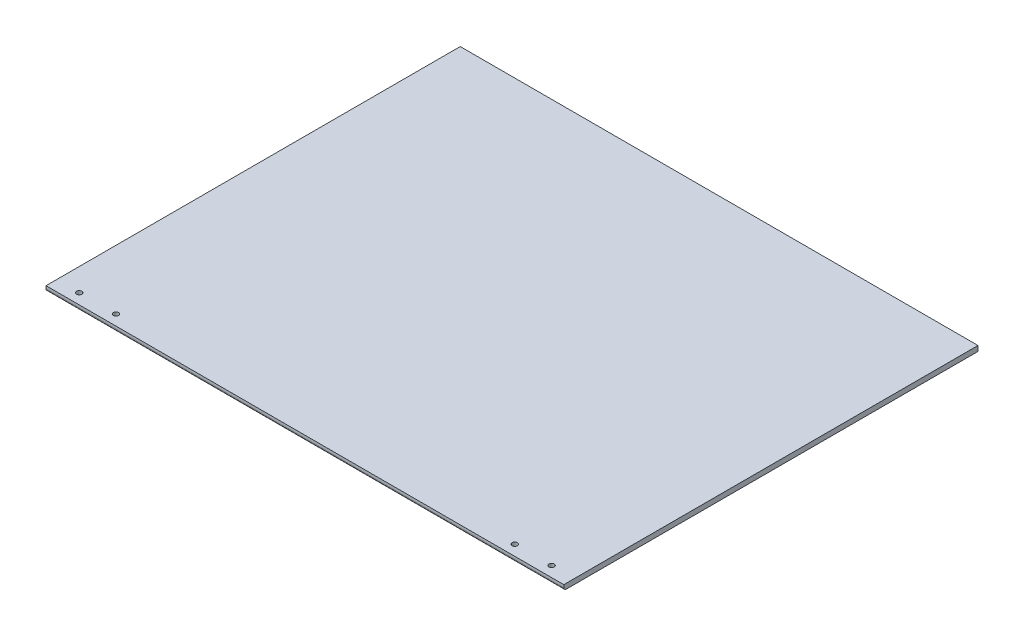
SolidWorks part; units mm, degrees
ref_plane "Front Plane" through (0, 0, 0) normal (0, 0, 1) x (1, 0, 0)
ref_plane "Top Plane" through (0, 0, 0) normal (0, 1, 0) x (1, 0, 0)
ref_plane "Right Plane" through (0, 0, 0) normal (1, 0, 0) x (0, 0, -1)
sketch "Sketch1" plane through (0, 0, 0) normal (0, 1, 0) x (1, 0, 0)
  line L1 (0, 0) -> (500, 0)
  line L2 (0, 0) -> (0, 400)
  line L3 (0, 400) -> (500, 400)
  line L4 (500, 0) -> (500, 400)
  dimension "D1" = 400
  dimension "D2" = 500
extrude "Boss-Extrude1" add sketch "Sketch1" along normal blind 5
ref_plane "Plane1" through (500, 5, 0) normal (0, 0, -1) x (-1, 0, 0)
sketch "Sketch3" plane through (0, 5, 0) normal (0, 1, 0) x (1, 0, 0)
  line L0 (0, 0) -> (500, 0) construction
  line L2 (250, 0) -> (250, 400)
  line L3 (500, 400) -> (0, 400) construction
  circle A0 centre (478.0925, 10.16) radius 2.54
  circle A1 centre (442.5325, 10.16) radius 2.54
  circle A2 centre (21.9075, 10.16) radius 2.54
  circle A3 centre (57.4675, 10.16) radius 2.54
  point P16 (460.3125, 0)
  dimension "D2" = 5.08
  dimension "D3" = 5.08
  dimension "D1" = 10.16
  dimension "D4" = 17.78
  dimension "D5" = 17.78
  dimension "D6" = 39.6875
extrude "Cut-Extrude1" cut sketch "Sketch3" against normal blind 10 contours A2 | A3 | A0 | A1 region at (478.0925, 5, -10.16) region at (442.5325, 5, -10.16) region at (21.9075, 5, -10.16) region at (57.4675, 5, -10.16)
fillet "Fillet1" radius 2.5 1 edges at (250, 0, 0) type face fillet first side face at (250, 2.5, 0) second side face at (442.5325, 0, -12.7)
